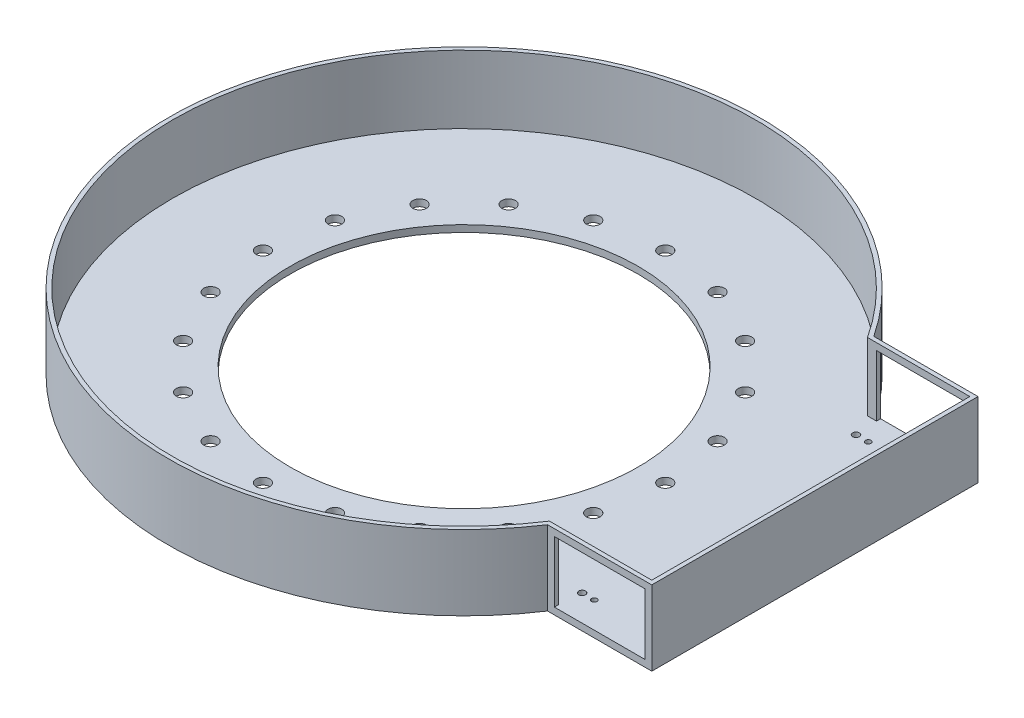
SolidWorks part; units mm, degrees
ref_plane "Plan de face" through (0, 0, 0) normal (0, 0, 1) x (1, 0, 0)
ref_plane "Plan de dessus" through (0, 0, 0) normal (0, 1, 0) x (1, 0, 0)
ref_plane "Plan de droite" through (0, 0, 0) normal (1, 0, 0) x (0, 0, -1)
sketch "Esquisse1" plane through (0, 0, 0) normal (0, 0, 1) x (1, 0, 0)
  line L0 (0, 0) -> (256, 0) construction
  line L1 (0, 0) -> (0, 51.0849) construction
  line L2 (256, 0) -> (336, 0)
  line L3 (256, 0) -> (256, 10)
  line L4 (256, 10) -> (336, 10)
  line L5 (336, 0) -> (336, 10)
  dimension "D1" = 80
  dimension "D2" = 10
  dimension "D3" = 256
revolve "Révolution1" add sketch "Esquisse1" angle 360 about L1
sketch "Esquisse3" plane through (0, 10, 0) normal (0, 1, 0) x (1, 0, 0)
  circle A0 centre (296, 0) radius 10
  dimension "D1" = 20
  dimension "D2" = 296
extrude "Enlèv. mat.-Extru.1" cut sketch "Esquisse3" against normal through all
pattern_circular "Répétition circulaire1" count 20 over 360 about axis through (0, 0, 0) along (0, -1, 0) of "Enlèv. mat.-Extru.1"
sketch "Esquisse4" plane through (0, 0, 0) normal (0, -1, 0) x (1, 0, 0)
  line L0 (0, 0) -> (538.9638, 0) construction
  line L1 (516.151, -240) -> (516.151, 240)
  line L2 (516.151, 240) -> (235.151, 240)
  line L4 (235.151, -240) -> (516.151, -240)
  circle A0 centre (0, 0) radius 336 construction
  arc A1 (235.151, -240) -> (235.151, 240) centre (0, 0) ccw
  point P6 (516.151, 0)
  dimension "D1" = 281
  dimension "D2" = 480
extrude "Boss.-Extru.1" add sketch "Esquisse4" against normal blind 10
sketch "Esquisse5" plane through (0, 0, 0) normal (0, -1, 0) x (1, 0, 0)
  line L0 (235.151, -240) -> (516.151, -240) construction
  line L1 (516.151, 240) -> (235.151, 240) construction
  line L2 (235.151, -240) -> (362.8016, -240)
  line L3 (362.8016, 240) -> (235.151, 240)
  arc A0 (362.8016, 240) -> (362.8016, -240) centre (0, 0) ccw
  arc A1 (235.151, 240) -> (235.151, -240) centre (0, 0) ccw construction
  arc A2 (235.151, 240) -> (235.151, -240) centre (0, 0) ccw
  dimension "D1" = 435
extrude "Boss.-Extru.2" add sketch "Esquisse5" against normal blind 10
sketch "Esquisse6" plane through (0, 10, 0) normal (0, 1, 0) x (1, 0, 0)
  line L6 (359.5622, -234) -> (510.151, -234)
  line L7 (510.151, -234) -> (510.151, 234)
  line L8 (510.151, 234) -> (359.5622, 234)
  line L9 (359.5622, -234) -> (510.151, -234)
  line L10 (510.151, -234) -> (510.151, 234)
  line L11 (510.151, 234) -> (359.5622, 234)
  arc A2 (359.5622, 234) -> (359.5622, -234) centre (0, 0) ccw
  arc A3 (359.5622, 234) -> (359.5622, -234) centre (0, 0) ccw
  arc M5 (362.8016, 240) -> (362.8016, -240) centre (0, 0) ccw
  line M6 (362.8016, -240) -> (516.151, -240)
  line M7 (516.151, -240) -> (516.151, 240)
  line M8 (516.151, 240) -> (362.8016, 240)
  dimension "D1" = 6
extrude "Boss.-Extru.3" add sketch "Esquisse6" along normal blind 100 contours A3 L11 L10 L9 M8 M5 M6 M7 region at (439.4763, 10, -238.711)
sketch "Esquisse8" plane through (0, 0, 240) normal (0, 0, 1) x (1, 0, 0)
  line L8 (372.8016, 100) -> (372.8016, 10)
  line L9 (372.8016, 10) -> (506.151, 10)
  line L10 (506.151, 10) -> (506.151, 100)
  line L11 (506.151, 100) -> (372.8016, 100)
  line L12 (372.8016, 100) -> (372.8016, 10)
  line L13 (372.8016, 10) -> (506.151, 10)
  line L14 (506.151, 10) -> (506.151, 100)
  line L15 (506.151, 100) -> (372.8016, 100)
  dimension "D1" = 10
extrude "Enlèv. mat.-Extru.2" cut sketch "Esquisse8" against normal through all
sketch "Esquisse9" plane through (0, 10, 0) normal (0, 1, 0) x (1, 0, 0)
  line L0 (510.151, -201.5) -> (500.151, -201.5) construction
  line L1 (510.151, -234) -> (510.151, 234) construction
  line L2 (500.151, -201.5) -> (500.151, -234) construction
  line L3 (359.5622, -234) -> (510.151, -234) construction
  line L4 (500.151, -201.5) -> (375.151, -201.5) construction
  line L5 (461.7094, -201.5) -> (461.7094, 201.5) construction
  circle A0 centre (500.151, -201.5) radius 5
  circle A1 centre (375.151, -201.5) radius 5
  circle A2 centre (393.151, -201.5) radius 4
  circle A3 centre (482.151, -201.5) radius 4
  circle A4 centre (375.151, 201.5) radius 5
  circle A5 centre (393.151, 201.5) radius 4
  circle A6 centre (482.151, 201.5) radius 4
  circle A7 centre (500.151, 201.5) radius 5
  point P16 (500.151, 0)
  point P20 (461.7094, 0)
  dimension "D3" = 10
  dimension "D5" = 10
  dimension "D6" = 8
  dimension "D7" = 8
  dimension "D1" = 10
  dimension "D2" = 32.5
  dimension "D4" = 125
  dimension "D8" = 18
  dimension "D9" = 18
  dimension "D10" = 403
extrude "Enlèv. mat.-Extru.3" cut sketch "Esquisse9" against normal through all
